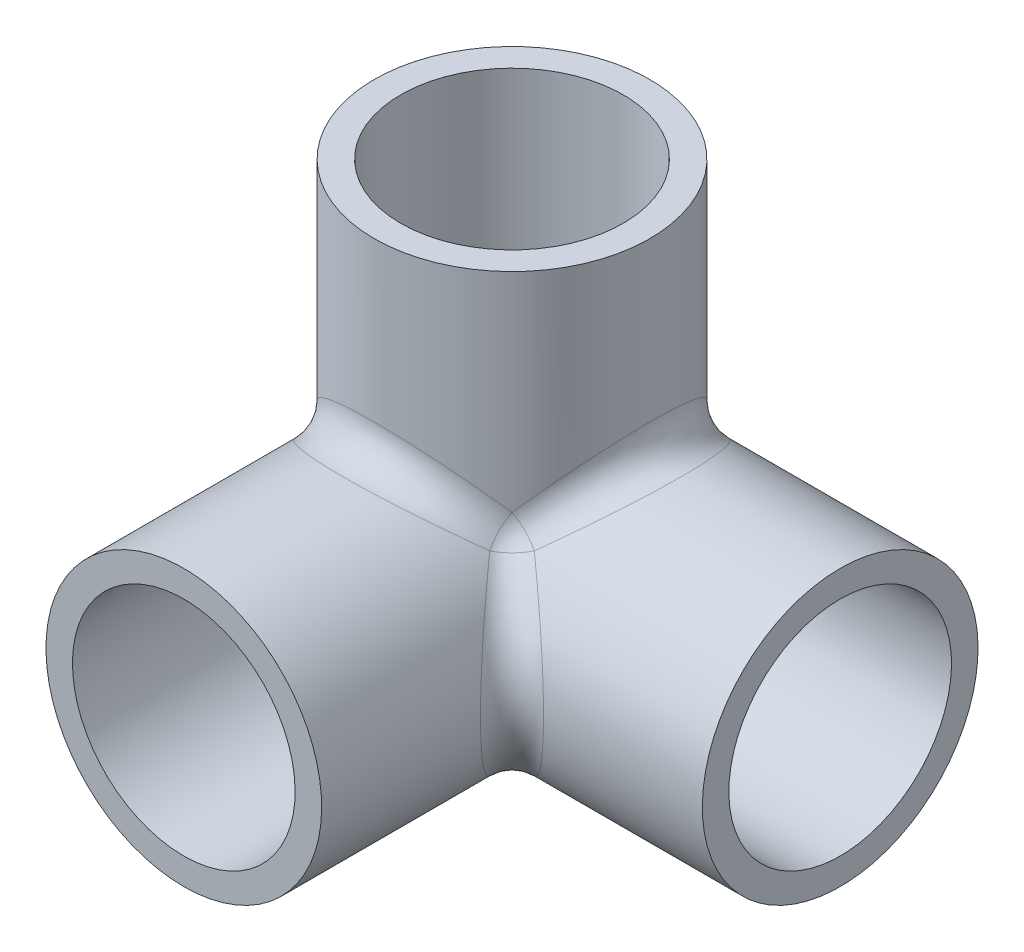
SolidWorks part; units mm, degrees
material "PVC Rigid"
ref_plane "Front Plane" through (0, 0, 0) normal (0, 0, 1) x (1, 0, 0)
ref_plane "Top Plane" through (0, 0, 0) normal (0, 1, 0) x (1, 0, 0)
ref_plane "Right Plane" through (0, 0, 0) normal (1, 0, 0) x (0, 0, -1)
sketch "Sketch1" plane through (0, 0, 0) normal (1, 0, 0) x (0, 0, -1)
  line L0 (0, 0) -> (-39.6875, 0) construction
  line L1 (0, 0) -> (0, 39.6875) construction
  line L2 (-39.6875, 16.6687) -> (-39.6875, -16.6688) construction
  line L3 (-16.6687, 39.6875) -> (16.6687, 39.6875) construction
  line L4 (-14.2875, -10.4648) -> (-14.2875, 10.4648) construction
  line L5 (-10.4648, 14.2875) -> (10.4648, 14.2875) construction
  line L6 (-14.2875, -10.4648) -> (-39.6875, -10.4648) construction
  line L7 (-26.9875, 13.462) -> (-26.9875, -13.462) construction
  line L8 (10.4648, 14.2875) -> (10.4648, 39.6875) construction
  line L9 (-13.462, 26.9875) -> (13.462, 26.9875) construction
  point P3 (-26.9875, -10.4648)
  point P7 (-39.6875, 0)
  point P10 (0, 39.6875)
  point P13 (-14.2875, 0)
  point P16 (0, 14.2875)
  point P20 (-26.9875, 0)
  point P21 (10.4648, 26.9875)
  point P25 (0, 26.9875)
  dimension "Leg Length" = 39.6875
  dimension "Elbow OD" = 33.3375
  dimension "Center to Socket" = 14.2875
  dimension "Pipe ID" = 20.9296
  dimension "For Pipe OD" = 26.924
  dimension "D1" = 14.2875
sketch "Sketch2" plane through (0, 0, 0) normal (0, 0, 1) x (1, 0, 0)
  line L0 (0, 0) -> (39.6875, 0) construction
  line L1 (0, 13.462) -> (0, -13.462) construction
  line L2 (39.6875, -16.6687) -> (39.6875, 16.6687) construction
  line L3 (14.2875, -10.4648) -> (14.2875, 10.4648) construction
  line L4 (26.9875, -13.462) -> (26.9875, 13.462) construction
  line L5 (0, 0) -> (0, 39.6875) construction
  line L6 (14.2875, 10.4648) -> (39.6875, 10.4648) construction
  point P7 (39.6875, 0)
  point P10 (14.2875, 0)
  point P13 (26.9875, 0)
  point P15 (26.9875, 10.4648)
  dimension "D1" = 14.2875
  dimension "D2" = 20.9296
  dimension "D3" = 33.3375
  dimension "D4" = 39.6875
  dimension "D5" = 26.924
sketch "Sketch3" plane through (0, 0, 0) normal (1, 0, 0) x (0, 0, -1)
  line L0 (-39.6875, 0) -> (-39.6875, -16.6688)
  line L1 (-39.6875, -16.6688) -> (0, -16.6688)
  line L2 (0, -16.6687) -> (0, 16.6687) construction
  line L3 (-39.6875, 0) -> (16.6687, 0)
  arc A0 (0, -16.6688) -> (16.6687, 0) centre (0, 0) ccw
revolve "Revolve1" add sketch "Sketch3" angle 360 about L3
sketch "Sketch4" plane through (0, 0, 0) normal (1, 0, 0) x (0, 0, -1)
  line L0 (16.6687, 39.6875) -> (0, 39.6875)
  line L1 (0, 39.6875) -> (0, -16.6687)
  line L2 (0, -16.6687) -> (0, 16.6687) construction
  line L3 (16.6687, 39.6875) -> (16.6687, 0)
  arc A0 (0, -16.6688) -> (0, 16.6688) centre (0, 0) ccw construction
  arc A1 (0, -16.6687) -> (16.6687, 0) centre (0, 0) ccw
revolve "Revolve2" add sketch "Sketch4" angle 360 about L1
sketch "Sketch5" plane through (0, 0, 0) normal (0, 0, 1) x (1, 0, 0)
  line L0 (39.6875, -16.6687) -> (0, -16.6688)
  line L1 (0, 16.6687) -> (0, -16.6688) construction
  line L2 (39.6875, -16.6687) -> (39.6875, 0)
  line L3 (39.6875, 0) -> (-16.6687, 0)
  circle A0 centre (0, 0) radius 16.6688 construction
  arc A1 (-16.6687, 0) -> (0, -16.6688) centre (0, 0) ccw
revolve "Revolve3" add sketch "Sketch5" angle 360 about L3
sketch "Sketch6" plane through (0, 0, 0) normal (1, 0, 0) x (0, 0, -1)
  line L0 (-39.6875, 0) -> (10.4648, 0)
  line L1 (-39.6875, -13.462) -> (-14.2875, -13.462)
  line L2 (-39.6875, 16.6687) -> (-39.6875, -16.6688) construction
  line L3 (-14.2875, -13.462) -> (-14.2875, -10.4648)
  line L4 (-14.2875, -10.4648) -> (0, -10.4648)
  line L5 (0, -13.462) -> (0, 13.462) construction
  line L6 (-39.6875, 0) -> (-39.6875, -13.462)
  arc A0 (10.4648, 0) -> (0, -10.4648) centre (0, 0) cw
revolve "Cut-Revolve1" cut sketch "Sketch6" angle 360 about L0
sketch "Sketch7" plane through (0, 0, 0) normal (1, 0, 0) x (0, 0, -1)
  line L0 (0, 39.6875) -> (13.462, 39.6875)
  line L1 (0, 39.6875) -> (0, -10.4648)
  line L2 (0, -13.462) -> (0, 13.462) construction
  line L3 (-16.6687, 39.6875) -> (16.6687, 39.6875) construction
  line L4 (13.462, 39.6875) -> (13.462, 14.2875)
  line L5 (13.462, 14.2875) -> (10.4648, 14.2875)
  line L6 (10.4648, 14.2875) -> (10.4648, 0)
  line L7 (0, 0) -> (-39.6875, 0) construction
  arc A0 (0, -10.4648) -> (10.4648, 0) centre (0, 0) ccw
revolve "Cut-Revolve2" cut sketch "Sketch7" angle 360 about L1
sketch "Sketch8" plane through (0, 0, 0) normal (0, 0, 1) x (1, 0, 0)
  line L0 (39.6875, -13.462) -> (14.2875, -13.462)
  line L1 (39.6875, -16.6687) -> (39.6875, 16.6687) construction
  line L2 (14.2875, -13.462) -> (14.2875, -10.4648)
  line L3 (14.2875, -10.4648) -> (0, -10.4648)
  line L4 (39.6875, -13.462) -> (39.6875, 0)
  line L5 (39.6875, 0) -> (-10.4648, 0)
  arc A0 (-10.4648, 0) -> (10.4648, 0) centre (0, 0) ccw construction
  arc A1 (-10.4648, 0) -> (0, -10.4648) centre (0, 0) ccw
revolve "Cut-Revolve3" cut sketch "Sketch8" angle 360 about L5
fillet "Fillet1" radius 3.81 3 edges at (15.3999, 15.3999, -6.3789) (15.3999, -6.3789, 15.3999) (-6.3789, 15.3999, 15.3999)
sketch "Sketch9" plane through (0, 0, 0) normal (1, 0, 0) x (0, 0, -1)
  line L0 (-39.6875, 13.462) -> (-14.2875, 13.462)
  line L1 (-39.6875, 16.6687) -> (-39.6875, -16.6688) construction
  line L2 (-14.2875, 13.462) -> (-14.2875, 10.4648)
  line L3 (-14.2875, 10.4648) -> (-10.4648, 10.4648)
  line L4 (-10.4648, 10.4648) -> (-10.4648, 14.2875)
  line L5 (-10.4648, 14.2875) -> (-13.462, 14.2875)
  line L6 (-13.462, 14.2875) -> (-13.462, 39.6875)
  line L7 (-16.6687, 39.6875) -> (16.6687, 39.6875) construction
  line L8 (-39.6875, -13.462) -> (-14.2875, -13.462)
  line L9 (-14.2875, -13.462) -> (-14.2875, -10.4648)
  line L10 (-14.2875, -10.4648) -> (0, -10.4648)
  line L11 (10.4648, 0) -> (10.4648, 14.2875)
  line L12 (10.4648, 14.2875) -> (13.462, 14.2875)
  line L13 (13.462, 14.2875) -> (13.462, 39.6875)
  circle A0 centre (0, 0) radius 10.4648 construction
  arc A1 (10.4648, 0) -> (-7.3997, 7.3997) centre (0, 0) ccw construction
  arc A2 (0, -10.4648) -> (10.4648, 0) centre (0, 0) ccw
sketch "Sketch10" plane through (0, 0, 39.6875) normal (0, 0, 1) x (1, 0, 0)
  circle A0 centre (0, 0) radius 13.462 construction
  circle A1 centre (0, 0) radius 13.462
  point P3 (0, -13.462)
  point P4 (13.462, 0)
  point P5 (-13.462, 0)
  point P6 (0, 13.462)
equation "\"D1@Sketch1\"=\"Center to Socket@Sketch1\""
equation "\"D1@Sketch2\"=\"Center to Socket@Sketch1\""
equation "\"D2@Sketch2\"=\"Pipe ID@Sketch1\""
equation "\"D3@Sketch2\"=\"Elbow OD@Sketch1\""
equation "\"D4@Sketch2\"=\"Leg Length@Sketch1\""
equation "\"D5@Sketch2\"=\"For Pipe OD@Sketch1\""
equation "\"D1@Fillet1\"=\"Elbow OD@Sketch1\"*0.1142857143"
